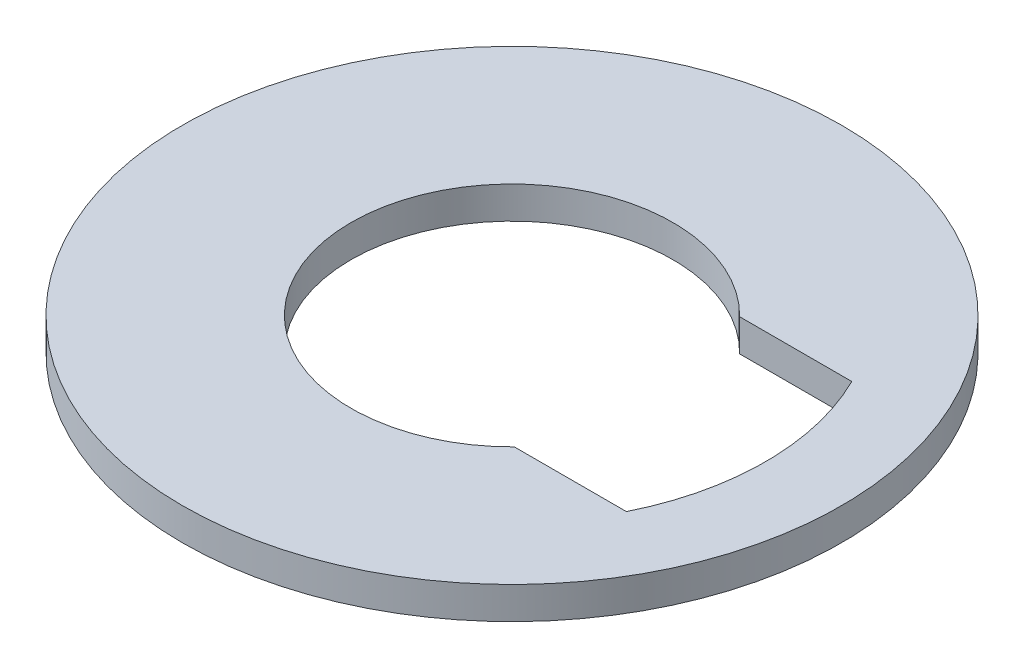
SolidWorks part; units mm, degrees
ref_plane "Front Plane" through (0, 0, 0) normal (0, 0, 1) x (1, 0, 0)
ref_plane "Top Plane" through (0, 0, 0) normal (0, 1, 0) x (1, 0, 0)
ref_plane "Right Plane" through (0, 0, 0) normal (1, 0, 0) x (0, 0, -1)
other "Bounding Box"
ref_plane "Default Plane" through (-8.9266, -12.7485, 0) normal (-0.1736, 0.9848, 0) x (0.9848, 0.1736, 0)
sketch "Sketch2" plane through (0, 0, 0) normal (1, 0, 0) x (0, 0, -1)
  line L0 (-25, 31.13) -> (25, 31.13) construction
  line L1 (-32.5, 31.13) -> (-25, 31.13)
  line L2 (-32.5, 31.13) -> (-32.5, 24.13)
  line L3 (-32.5, 24.13) -> (-25, 24.13)
  line L4 (-25, 31.13) -> (-25, 24.13)
  line L5 (-32.5, 31.13) -> (-25, 24.13) construction
  line L6 (-32.5, 24.13) -> (-25, 31.13) construction
  line L7 (25, 31.13) -> (32.5, 31.13)
  line L8 (25, 31.13) -> (25, 24.13)
  line L9 (25, 24.13) -> (32.5, 24.13)
  line L10 (32.5, 31.13) -> (32.5, 24.13)
  line L11 (25, 31.13) -> (32.5, 24.13) construction
  line L12 (25, 24.13) -> (32.5, 31.13) construction
  line L13 (-25, 24.13) -> (25, 24.13) construction
  line L14 (0, 0) -> (0, 24.13) construction
  line L15 (-25, 52.055) -> (25, 52.055) construction
  line L16 (25, 59.055) -> (-25, 59.055) construction
  line L17 (0, 31.13) -> (0, 52.055) construction
  line L18 (-32.5, 59.055) -> (-25, 59.055)
  line L19 (-32.5, 59.055) -> (-32.5, 52.055)
  line L20 (-32.5, 52.055) -> (-25, 52.055)
  line L21 (-25, 59.055) -> (-25, 52.055)
  line L22 (-32.5, 59.055) -> (-25, 52.055) construction
  line L23 (-32.5, 52.055) -> (-25, 59.055) construction
  line L24 (32.5, 59.055) -> (25, 59.055)
  line L25 (32.5, 59.055) -> (32.5, 52.055)
  line L26 (32.5, 52.055) -> (25, 52.055)
  line L27 (25, 59.055) -> (25, 52.055)
  line L28 (32.5, 59.055) -> (25, 52.055) construction
  line L29 (32.5, 52.055) -> (25, 59.055) construction
  line L34 (-77.1082, -22.225) -> (-30.51, -22.225) construction
  line L35 (-32.5, 31.13) -> (32.5, 31.13)
  line L36 (-32.5, 31.13) -> (-32.5, 37.48)
  line L37 (-32.5, 37.48) -> (32.5, 37.48)
  line L38 (32.5, 31.13) -> (32.5, 37.48)
  line L40 (-97.0753, 79.375) -> (-40, 79.375) construction
  circle A0 centre (0, 0) radius 22.225
  circle A1 centre (0, 0) radius 18
  circle A2 centre (0, 41.275) radius 14
  point P3 (-28.75, 27.63)
  point P8 (28.75, 27.63)
  point P16 (-28.75, 55.555)
  point P19 (15.875, 26.9233)
  point P22 (28.75, 55.555)
  point P31 (0, -1.6569)
  point P32 (-1.8597, 35.5113)
  point P33 (0, 35.56)
  point P36 (-14, 41.275)
  point P37 (-18, 0)
  point P39 (-22.225, 0)
  dimension "D1" = 44.45
  dimension "D5" = 36
  dimension "D6" = 28
  dimension "D7" = 81.28
  dimension "D8" = 34.925
  dimension "D2" = 65
  dimension "D3" = 50
  dimension "D4" = 7
  dimension "D9" = 6.35
  dimension "D10" = 41.275
  dimension "D14" = 101.6
sketch "Sketch3" plane through (0, 0, 0) normal (0, 1, 0) x (1, 0, 0)
  line L0 (-17.3, 0) -> (12.7, 0) construction
  line L6 (-9.525, 22.225) -> (9.525, 22.225)
  line L7 (-17.3, 14) -> (12.7, 14)
  line L8 (-17.3, 14) -> (-17.3, -14)
  line L9 (-17.3, -14) -> (12.7, -14)
  line L10 (12.7, 14) -> (12.7, -14)
  line L11 (-17.3, 14) -> (12.7, -14) construction
  line L12 (-17.3, -14) -> (12.7, 14) construction
  line L13 (-9.525, 22.225) -> (-9.525, -22.225)
  line L14 (-9.525, -22.225) -> (9.525, -22.225)
  line L20 (9.525, 22.225) -> (9.525, -22.225)
  line L21 (-9.525, 22.225) -> (9.525, -22.225) construction
  line L22 (14.7, 9.017) -> (21.7, 9.017)
  line L23 (14.7, 9.017) -> (14.7, -9.017)
  line L24 (14.7, -9.017) -> (21.7, -9.017)
  line L25 (21.7, 9.017) -> (21.7, -9.017)
  line L26 (14.7, 9.017) -> (21.7, -9.017) construction
  line L27 (14.7, -9.017) -> (21.7, 9.017) construction
  line L32 (-9.525, -22.225) -> (9.525, 22.225) construction
  line L33 (-24.3, 18) -> (12.7, 18)
  line L34 (-24.3, 18) -> (-24.3, -18)
  line L39 (-24.3, -18) -> (12.7, -18)
  line L40 (12.7, 18) -> (12.7, -18)
  line L45 (-24.3, 18) -> (12.7, -18) construction
  line L46 (-24.3, -18) -> (12.7, 18) construction
  line L47 (21.7, -9.017) -> (32.2514, -9.017)
  line L48 (21.7, -9.017) -> (21.7, 9.017)
  line L49 (21.7, 9.017) -> (32.2514, 9.017)
  line L50 (32.2514, -9.017) -> (32.2514, 9.017)
  line L51 (21.7, -9.017) -> (32.2514, 9.017) construction
  line L52 (21.7, 9.017) -> (32.2514, -9.017) construction
  circle A0 centre (0, 0) radius 25
  circle A1 centre (0, 0) radius 32.5
  point P3 (0, 0)
  point P5 (-2.3, 0)
  point P8 (-5.8, 0)
  point P22 (33.447, -9.017)
  point P23 (25, -9.017)
  point P27 (0, 0)
  point P28 (0, 0)
  point P29 (18.2, 0)
  point P34 (-4.1552, 0)
  point P35 (0, 0)
  point P36 (0, 0)
  point P37 (-2.4012, 0)
  point P38 (-24.7652, -18)
  point P50 (26.9757, 0)
  dimension "D6" = 17.5514
  dimension "D1" = 30
  dimension "D2" = 18.034
  dimension "D3" = 19.05
  dimension "D4" = 37
  dimension "D5" = 7
  dimension "D7" = 2
  dimension "D8" = 12.7
ref_plane "Plane1" through (0, 24.13, 0) normal (0, 1, 0) x (1, 0, 0)
sketch "Sketch4" plane through (0, 24.13, 0) normal (0, 1, 0) x (1, 0, 0)
  line L0 (22.3945, 11.1125) -> (11.337, 11.1125)
  line L1 (22.3945, -11.1125) -> (11.337, -11.1125)
  line L2 (15.875, 0) -> (25, 0) construction
  line L3 (16.8657, -11.1125) -> (16.8657, 0) construction
  line L4 (16.8657, 0) -> (16.8657, 11.1125) construction
  circle A0 centre (0, 0) radius 32.5
  circle A1 centre (0, 0) radius 32.5 construction
  arc A2 (11.337, 11.1125) -> (11.337, -11.1125) centre (0, 0) ccw
  arc A3 (22.3945, -11.1125) -> (22.3945, 11.1125) centre (0, 0) ccw
  circle A4 centre (0, 0) radius 25 construction
  arc A5 (11.337, -11.1125) -> (15.875, 0) centre (0, 0) ccw construction
  arc A6 (15.875, 0) -> (11.337, 11.1125) centre (0, 0) ccw construction
  dimension "D1" = 31.75
  dimension "D2" = 22.225
extrude "Boss-Extrude1" add sketch "Sketch4" against normal blind 3.175
